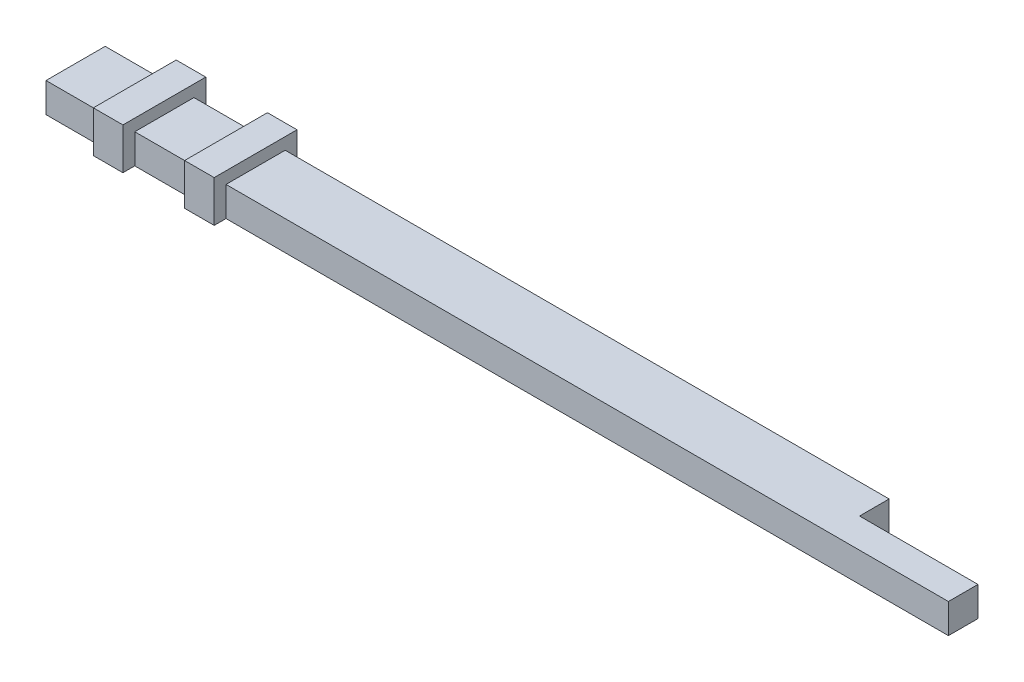
SolidWorks part; units mm, degrees
ref_plane "Front Plane" through (0, 0, 0) normal (0, 0, 1) x (1, 0, 0)
ref_plane "Top Plane" through (0, 0, 0) normal (0, 1, 0) x (1, 0, 0)
ref_plane "Right Plane" through (0, 0, 0) normal (1, 0, 0) x (0, 0, -1)
sketch "Sketch1" plane through (0, 0, 0) normal (0, 1, 0) x (1, 0, 0)
  line L0 (132.4815, 10) -> (132.4815, 5)
  line L1 (0, 0) -> (142.5, 0)
  line L2 (0, 0) -> (0, 10)
  line L3 (0, 10) -> (132.4815, 10)
  line L5 (142.5, 0) -> (152.5, 0)
  line L7 (142.4815, 5) -> (152.5, 5)
  line L8 (152.5, 0) -> (152.5, 5)
  line L9 (132.4815, 5) -> (142.4815, 5)
  dimension "D1" = 142.5
  dimension "D2" = 10
  dimension "D3" = 10
  dimension "D4" = 10
extrude "Boss-Extrude1" add sketch "Sketch1" along normal blind 5
ref_plane "Plane1" through (10, 0, 0) normal (-1, 0, 0) x (0, 0, 1)
sketch "Sketch2" plane through (10, 0, 0) normal (-1, 0, 0) x (0, 0, 1)
  line L0 (-10, 5) -> (0, 5) construction
  line L1 (-12, 7) -> (2, 7)
  line L2 (-12, 7) -> (-12, 0)
  line L3 (-12, 0) -> (2, 0)
  line L4 (2, 7) -> (2, 0)
  line L5 (-10, 0) -> (0, 0) construction
  line L6 (0, 5) -> (0, 0) construction
  line L7 (-10, 5) -> (-10, 0) construction
  dimension "D1" = 2
  dimension "D2" = 0
  dimension "D3" = 2
  dimension "D4" = 2
extrude "Boss-Extrude2" add sketch "Sketch2" against normal blind 5
ref_plane "Plane2" through (30.42, 0, 0) normal (1, 0, 0) x (0, 0, -1)
sketch "Sketch3" plane through (30.42, 0, 0) normal (1, 0, 0) x (0, 0, -1)
  line L1 (-2, 7) -> (12, 7)
  line L2 (-2, 7) -> (-2, 0)
  line L3 (-2, 0) -> (12, 0)
  line L4 (12, 7) -> (12, 0)
extrude "Boss-Extrude3" add sketch "Sketch3" against normal blind 5
